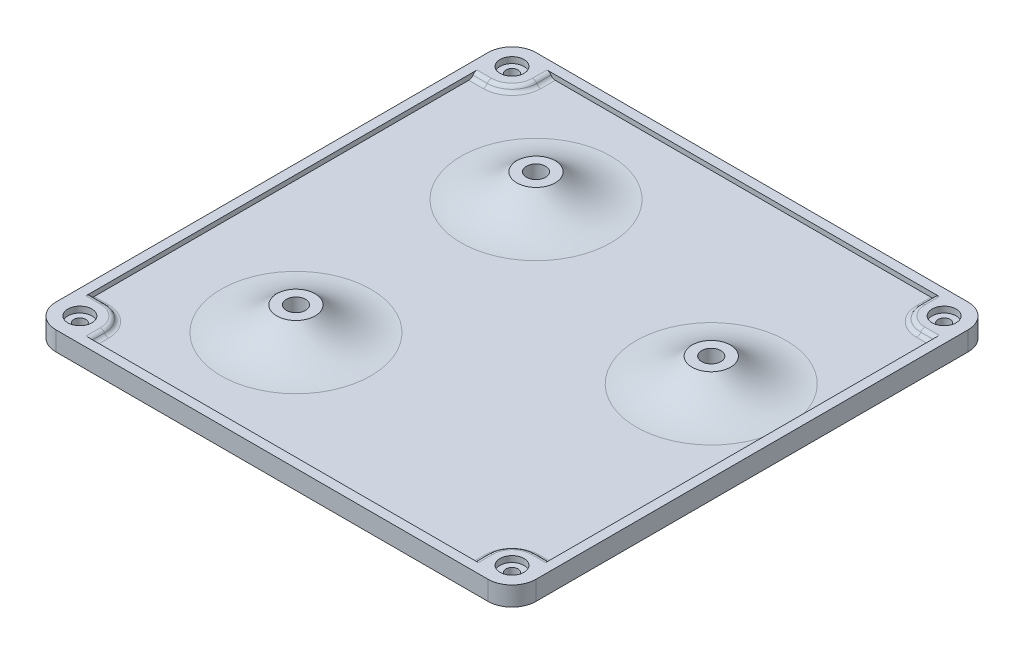
SolidWorks part; units mm, degrees
ref_plane "Front Plane" through (0, 0, 0) normal (0, 0, 1) x (1, 0, 0)
ref_plane "Top Plane" through (0, 0, 0) normal (0, 1, 0) x (1, 0, 0)
ref_plane "Right Plane" through (0, 0, 0) normal (1, 0, 0) x (0, 0, -1)
sketch "Sketch1" plane through (0, 0, 0) normal (0, 1, 0) x (1, 0, 0)
  line L1 (50, 50) -> (-50, 50)
  line L2 (50, 50) -> (50, -50)
  line L3 (50, -50) -> (-50, -50)
  line L4 (-50, 50) -> (-50, -50)
  line L5 (50, 50) -> (-50, -50) construction
  line L6 (50, -50) -> (-50, 50) construction
  point P0 (0, 0)
extrude "Boss-Extrude1" add sketch "Sketch1" along normal blind 4
sketch "Sketch2" plane through (0, 4, 0) normal (0, 1, 0) x (1, 0, 0)
  line L1 (48, 48) -> (-48, 48)
  line L2 (48, 48) -> (48, -48)
  line L3 (48, -48) -> (-48, -48)
  line L4 (-48, 48) -> (-48, -48)
  line L5 (48, 48) -> (-48, -48) construction
  line L6 (48, -48) -> (-48, 48) construction
  point P0 (0, 0)
extrude "Cut-Extrude1" cut sketch "Sketch2" against normal blind 1
sketch "Sketch7" plane through (0, 3, 0) normal (0, 1, 0) x (1, 0, 0)
  line L1 (-48, 48) -> (-40, 48)
  line L2 (-48, 48) -> (-48, 40)
  line L3 (-48, 40) -> (-40, 40)
  line L4 (-40, 48) -> (-40, 40)
  line L5 (-48, 48) -> (-40, 40) construction
  line L6 (-48, 40) -> (-40, 48) construction
  point P0 (-44, 44)
extrude "Boss-Extrude4" add sketch "Sketch7" along normal blind 1
sketch "Sketch9" plane through (0, 3, 0) normal (0, 1, 0) x (1, 0, 0)
  line L1 (48, 48) -> (40, 48)
  line L2 (48, 48) -> (48, 40)
  line L3 (48, 40) -> (40, 40)
  line L4 (40, 48) -> (40, 40)
  line L5 (48, 48) -> (40, 40) construction
  line L6 (48, 40) -> (40, 48) construction
  point P0 (44, 44)
extrude "Boss-Extrude5" add sketch "Sketch9" along normal blind 1
sketch "Sketch10" plane through (0, 3, 0) normal (0, 1, 0) x (1, 0, 0)
  line L1 (-48, -48) -> (-40, -48)
  line L2 (-48, -48) -> (-48, -40)
  line L3 (-48, -40) -> (-40, -40)
  line L4 (-40, -48) -> (-40, -40)
  line L5 (-48, -48) -> (-40, -40) construction
  line L6 (-48, -40) -> (-40, -48) construction
  point P0 (-44, -44)
extrude "Boss-Extrude6" add sketch "Sketch10" along normal blind 1
sketch "Sketch11" plane through (0, 3, 0) normal (0, 1, 0) x (1, 0, 0)
  line L1 (48, -48) -> (40, -48)
  line L2 (48, -48) -> (48, -40)
  line L3 (48, -40) -> (40, -40)
  line L4 (40, -48) -> (40, -40)
  line L5 (48, -48) -> (40, -40) construction
  line L6 (48, -40) -> (40, -48) construction
  point P0 (44, -44)
extrude "Boss-Extrude7" add sketch "Sketch11" along normal blind 1
fillet "Fillet8" radius 5 1 edges at (-40, 3.5, -40)
fillet "Fillet9" radius 5 1 edges at (-40, 3.5, 40)
fillet "Fillet10" radius 5 1 edges at (40, 3.5, 40)
fillet "Fillet11" radius 5 1 edges at (40, 3.5, -40)
fillet "Fillet12" radius 5 1 edges at (50, 2, -50)
fillet "Fillet13" radius 5 1 edges at (50, 2, 50)
fillet "Fillet14" radius 5 1 edges at (-50, 2, 50)
fillet "Fillet15" radius 5 1 edges at (-50, 2, -50)
fillet "Fillet18" radius 1 3 edges at (-40, 3, -46.5) (-46.5, 3, -40) (-41.4645, 3, -41.4645)
fillet "Fillet19" radius 1 3 edges at (-46.5, 4, -40) (-40, 4, -46.5) (-41.4645, 4, -41.4645)
fillet "Fillet20" radius 1 3 edges at (40, 4, -46.5) (46.5, 4, -40) (41.4645, 4, -41.4645)
fillet "Fillet21" radius 1 3 edges at (46.5, 3, -40) (40, 3, -46.5) (41.4645, 3, -41.4645)
fillet "Fillet22" radius 1 3 edges at (-46.5, 3, 40) (-40, 3, 46.5) (-41.4645, 3, 41.4645)
fillet "Fillet23" radius 1 3 edges at (-40, 4, 46.5) (-46.5, 4, 40) (-41.4645, 4, 41.4645)
fillet "Fillet24" radius 1 3 edges at (46.5, 4, 40) (40, 4, 46.5) (41.4645, 4, 41.4645)
fillet "Fillet25" radius 1 3 edges at (40, 3, 46.5) (46.5, 3, 40) (41.4645, 3, 41.4645)
sketch "Sketch15" plane through (0, 4, 0) normal (0, 1, 0) x (1, 0, 0)
  circle A0 centre (-45, 45) radius 2.5
extrude "Cut-Extrude7" cut sketch "Sketch15" against normal blind 1.25
sketch "Sketch16" plane through (0, 0, 0) normal (0, -1, 0) x (1, 0, 0)
  circle A0 centre (-45, -45) radius 2.5
extrude "Cut-Extrude8" cut sketch "Sketch16" against normal blind 1.25
sketch "Sketch17" plane through (0, 2.75, 0) normal (0, 1, 0) x (1, 0, 0)
  circle A0 centre (-45, 45) radius 1.1
extrude "Cut-Extrude9" cut sketch "Sketch17" against normal blind 1.5
sketch "Sketch18" plane through (0, 4, 0) normal (0, 1, 0) x (1, 0, 0)
  circle A0 centre (45, 45) radius 2.5
extrude "Cut-Extrude10" cut sketch "Sketch18" against normal blind 1.25
sketch "Sketch19" plane through (0, 0, 0) normal (0, -1, 0) x (1, 0, 0)
  circle A0 centre (45, -45) radius 2.5
extrude "Cut-Extrude11" cut sketch "Sketch19" against normal blind 1.25
sketch "Sketch20" plane through (0, 2.75, 0) normal (0, 1, 0) x (1, 0, 0)
  circle A0 centre (45, 45) radius 1.05
extrude "Cut-Extrude12" cut sketch "Sketch20" against normal through all
sketch "Sketch21" plane through (0, 4, 0) normal (0, 1, 0) x (1, 0, 0)
  circle A0 centre (-45, -45) radius 2.5
extrude "Cut-Extrude13" cut sketch "Sketch21" against normal blind 1.25
sketch "Sketch23" plane through (0, 0, 0) normal (0, -1, 0) x (-1, 0, 0)
  circle A0 centre (45, -45) radius 2.5
extrude "Cut-Extrude14" cut sketch "Sketch23" against normal blind 1.25
sketch "Sketch24" plane through (0, 2.75, 0) normal (0, 1, 0) x (1, 0, 0)
  circle A0 centre (-45, -45) radius 1.05
extrude "Cut-Extrude15" cut sketch "Sketch24" against normal through all
sketch "Sketch25" plane through (0, 0, 0) normal (0, -1, 0) x (1, 0, 0)
  circle A0 centre (45, 45) radius 2.5
extrude "Cut-Extrude16" cut sketch "Sketch25" against normal blind 1.25
sketch "Sketch26" plane through (0, 4, 0) normal (0, 1, 0) x (1, 0, 0)
  circle A0 centre (45, -45) radius 2.5
extrude "Cut-Extrude17" cut sketch "Sketch26" against normal blind 1.25
sketch "Sketch27" plane through (0, 2.75, 0) normal (0, 1, 0) x (1, 0, 0)
  circle A0 centre (45, -45) radius 1.05
  point P3 (0, 0)
  point P4 (0, 0)
extrude "Cut-Extrude18" cut sketch "Sketch27" against normal through all
sketch "Sketch28" plane through (0, 3, 0) normal (0, 1, 0) x (1, 0, 0)
  circle A0 centre (-19.5, 24.5) radius 4
sketch "Sketch31" plane through (0, 3, 0) normal (0, 1, 0) x (1, 0, 0)
  circle A0 centre (-20.5, -24.5) radius 4
sketch "Sketch33" plane through (0, 3, 0) normal (0, 1, 0) x (1, 0, 0)
  circle A0 centre (32, 9.5) radius 4
extrude "Boss-Extrude9" add sketch "Sketch28" along normal blind 5
extrude "Boss-Extrude10" add sketch "Sketch31" along normal blind 5
extrude "Boss-Extrude11" add sketch "Sketch33" along normal blind 5
sketch "Sketch39" plane through (0, 8, 0) normal (0, 1, 0) x (1, 0, 0)
  circle A0 centre (-19.5, 24.5) radius 2
extrude "Cut-Extrude22" cut sketch "Sketch39" against normal blind 5.45
sketch "Sketch40" plane through (0, 8, 0) normal (0, 1, 0) x (1, 0, 0)
  circle A0 centre (32, 9.5) radius 2
extrude "Cut-Extrude23" cut sketch "Sketch40" against normal blind 5.45
sketch "Sketch41" plane through (0, 8, 0) normal (0, 1, 0) x (1, 0, 0)
  circle A0 centre (-20.5, -24.5) radius 2
extrude "Cut-Extrude24" cut sketch "Sketch41" against normal blind 5.45
fillet "Fillet27" radius 16 3 edges at (-20.5, 3, 20.5) (32, 3, -13.5) (-19.5, 3, -28.5)
sketch "Sketch42" plane through (0, 2.75, 0) normal (0, 1, 0) x (1, 0, 0)
  circle A0 centre (45, -45) radius 1.25
extrude "Cut-Extrude25" cut sketch "Sketch42" against normal through all
sketch "Sketch43" plane through (0, 2.75, 0) normal (0, 1, 0) x (1, 0, 0)
  circle A0 centre (-45, 45) radius 1.25
extrude "Cut-Extrude26" cut sketch "Sketch43" against normal through all
sketch "Sketch44" plane through (0, 2.75, 0) normal (0, 1, 0) x (1, 0, 0)
  circle A0 centre (-45, -45) radius 1.25
extrude "Cut-Extrude27" cut sketch "Sketch44" against normal through all
sketch "Sketch45" plane through (0, 2.75, 0) normal (0, 1, 0) x (1, 0, 0)
  circle A0 centre (45, 45) radius 1.25
extrude "Cut-Extrude28" cut sketch "Sketch45" against normal through all
